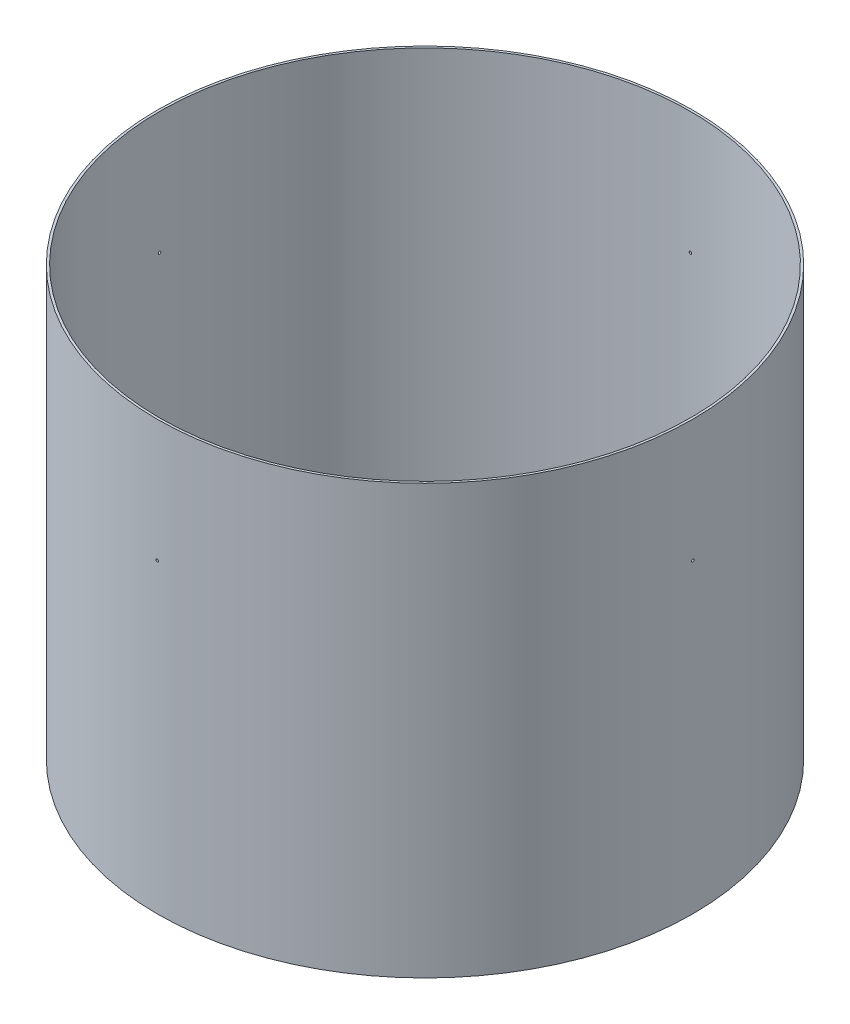
SolidWorks part; units mm, degrees
material "2014 Alloy"
ref_plane "Front Plane" through (0, 0, 0) normal (0, 0, 1) x (1, 0, 0)
ref_plane "Top Plane" through (0, 0, 0) normal (0, 1, 0) x (1, 0, 0)
ref_plane "Right Plane" through (0, 0, 0) normal (1, 0, 0) x (0, 0, -1)
sketch "Sketch9" plane through (0, 0, 0) normal (0, 1, 0) x (1, 0, 0)
  circle A0 centre (0, 0) radius 1750
extrude "Boss-Extrude5" add sketch "Sketch9" along normal blind 2800
sketch "Sketch19" plane through (0, 0, 0) normal (0, 0, 1) x (1, 0, 0)
  circle A0 centre (0, 2000) radius 8.382
extrude "Cut-Extrude11" cut sketch "Sketch19" along normal blind 300 and the other way blind 100 from offset 1800
sketch "Sketch20" plane through (0, 2800, 0) normal (0, 1, 0) x (1, 0, 0)
  circle A0 centre (0, 0) radius 1735
extrude "Cut-Extrude12" cut sketch "Sketch20" against normal blind 2785
pattern_circular "CirPattern1" count 4 every 90 about axis through (0, 2800, 0) along (0, -1, 0) of "Cut-Extrude11"
